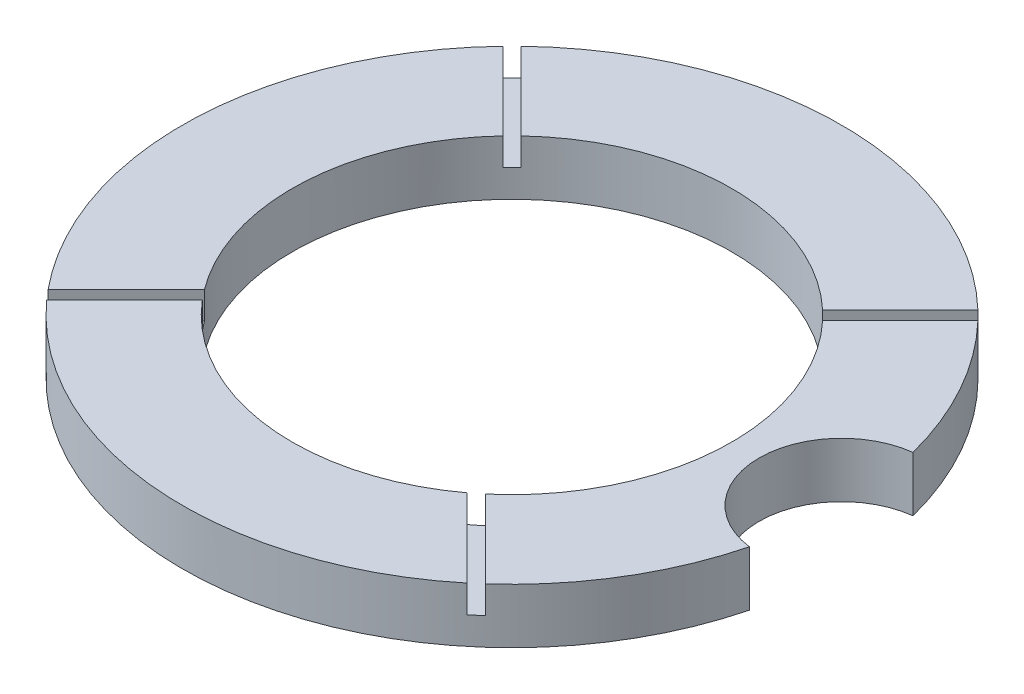
SolidWorks part; units mm, degrees
ref_plane "Front Plane" through (0, 0, 0) normal (0, 0, 1) x (1, 0, 0)
ref_plane "Top Plane" through (0, 0, 0) normal (0, 1, 0) x (1, 0, 0)
ref_plane "Right Plane" through (0, 0, 0) normal (1, 0, 0) x (0, 0, -1)
sketch "Sketch1" plane through (0, 0, 0) normal (0, 1, 0) x (1, 0, 0)
  circle A0 centre (0, 0) radius 50.8
  circle A1 centre (0, 0) radius 76.1746
  dimension "D1" = 101.6
  dimension "D2" = 152.3492
extrude "Boss-Extrude1" add sketch "Sketch1" along normal blind 12.7 contours A1
extrude "Cut-Extrude2" cut sketch "Sketch1<10>" along normal through all contours A0
sketch "Sketch1<10>" plane through (0, 0, 0) normal (0, 1, 0) x (1, 0, 0) same geometry as "Sketch1"
sketch "Sketch2" plane through (0, 12.7, 0) normal (0, 1, 0) x (1, 0, 0)
  line L0 (76.2, 19.05) -> (76.2, -19.05)
  arc A0 (76.2, 19.05) -> (76.2, -19.05) centre (76.1746, 0) ccw
  circle A1 centre (0, 0) radius 76.1746 construction
  dimension "D1" = 38.1
extrude "Cut-Extrude3" cut sketch "Sketch2" against normal through all contours A0 L0
sketch "Sketch3" plane through (0, 12.7, 0) normal (0, 1, 0) x (1, 0, 0)
  line L0 (0, 0) -> (0, 21.8013) construction
  line L1 (0, 0) -> (-17.1561, 17.1561) construction
  line L2 (-35.921, 35.921) -> (-53.8636, 53.8636) construction
  line L3 (-31.9733, 29.8539) -> (-29.8539, 31.9733)
  line L4 (-31.9733, 29.8539) -> (-59.9307, 57.8113)
  line L5 (-29.8539, 31.9733) -> (-57.8113, 59.9307)
  line L6 (-59.9307, 57.8113) -> (-57.8113, 59.9307)
  line L7 (-31.9733, 29.8539) -> (-57.8113, 59.9307) construction
  line L8 (-29.8539, 31.9733) -> (-59.9307, 57.8113) construction
  line L9 (27.8513, 25.732) -> (55.8087, 53.6894)
  line L10 (53.6894, 55.8087) -> (55.8087, 53.6894)
  line L11 (25.732, 27.8513) -> (53.6894, 55.8087)
  line L12 (21.61, -31.9733) -> (49.5675, -59.9307)
  line L13 (51.6868, -57.8113) -> (49.5675, -59.9307)
  line L14 (23.7294, -29.8539) -> (51.6868, -57.8113)
  line L15 (-36.0952, -25.732) -> (-64.0526, -53.6894)
  line L16 (-61.9333, -55.8087) -> (-64.0526, -53.6894)
  line L17 (-33.9759, -27.8513) -> (-61.9333, -55.8087)
  line L18 (25.732, 27.8513) -> (27.8513, 25.732)
  line L19 (23.7294, -29.8539) -> (21.61, -31.9733)
  line L20 (-36.0952, -25.732) -> (-33.9759, -27.8513)
  circle A0 centre (0, 0) radius 50.8 construction
  circle A1 centre (0, 0) radius 76.1746 construction
  point P12 (-44.8923, 44.8923)
  point P13 (-44.8923, 44.8923)
  point P31 (-4.1219, 0)
  dimension "D1" = 45
  dimension "D2" = 2.9972
  dimension "D3" = 4
extrude "Cut-Extrude4" cut sketch "Sketch3" against normal blind 6.35
equation "\"Bodytube_OD\" = 6.17in"
equation "\"Bodytube_ID\" = 5.998in"
equation "\"Motor_OD\" = 4in"
equation "\"Fwd_Tube_Length\" = 38in"
equation "\"Mid_Tube_Length\" = 8in"
equation "\"Aft_Section_Length\"= 40in"
equation "\"Mid_Coupler_Length\" = 13in"
equation "\"Aft_Lower_Length\"= 22in"
equation "\"AB_Coupler_OD_Length\"= 1in"
equation "\"AB_Coupling_Section_Length\"= 0.375in"
equation "\"AB_Coupler_Length\"= \"AB_Coupler_OD_Length\" + \"AB_Coupling_Section_Length\" * 2"
equation "\"Cutout_Angle\" = 80"
equation "\"AB_Paddle_Height\" = 0.375in"
equation "\"AB_Coupler_Num_Screws\"= 6"
equation "\"Num_Cutouts\" = 3"
equation "\"AB_Coupler_OD\"= 6.17in"
equation "\"AB_Coupler_ID\"= 5.75in"
equation "\"AB_Coupler_Surface_Diameter\"= 5.998in"
equation "\"AB_Coupling_Screw_Diameter\"= 0.1065in"
equation "\"AB_Central_Bushing_Length\" = .75in"
equation "\"Lead_Screw_Dist\" = 2.25in"
equation "\"Lead_Screw_Diam\" = (27/64)*1in"
equation "\"Lead_Screw_Length\" = (\"Mid_Coupler_Length\" + 2*0.375in + 2*0.5in)"
equation "\"Paddle_Pin_Offset\" = .25in"
equation "\"Paddle_Pin_Radius\" = 2.25in"
equation "\"Paddle_Gear_OD\" = 3.2in"
equation "\"Fwd_BKHD_From_Top\" = 18in"
equation "\"D2@Sketch1\"=\"Bodytube_ID\""
equation "\"D1@Sketch1\"=\"Motor_OD\""
equation "\"Fin_Thickness\"= .118in"
equation "\"Guiderail_Cutout_Diameter\"= 1.5in"
equation "\"D1@Sketch2\"=\"Guiderail_Cutout_Diameter\""
equation "\"D2@Sketch3\"=\"Fin_Thickness\""
